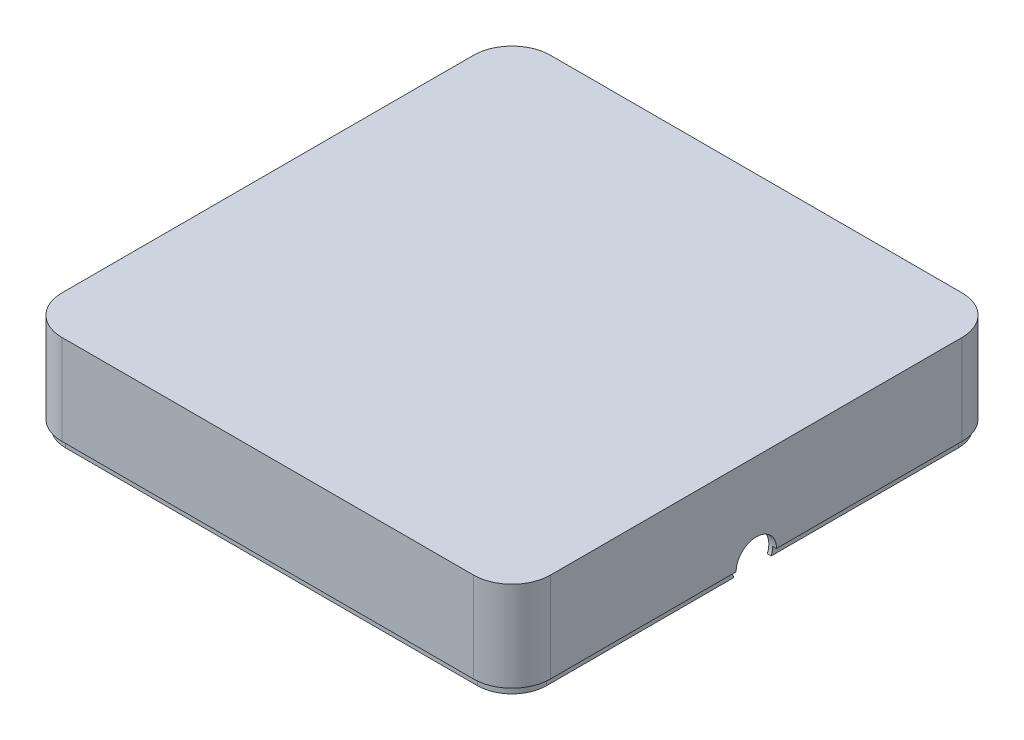
SolidWorks part; units mm, degrees
ref_plane "Front" through (0, 0, 0) normal (0, 0, 1) x (1, 0, 0)
ref_plane "Top" through (0, 0, 0) normal (0, 1, 0) x (1, 0, 0)
ref_plane "Right" through (0, 0, 0) normal (1, 0, 0) x (0, 0, -1)
sketch "Sketch1" plane through (0, 0, 0) normal (0, 0, 1) x (1, 0, 0)
  line L1 (0, 0) -> (127, 0)
  line L2 (0, 0) -> (0, -25.4)
  line L3 (0, -25.4) -> (127, -25.4)
  line L4 (127, 0) -> (127, -25.4)
  dimension "D1" = 127
  dimension "D2" = 25.4
extrude "Boss-Extrude1" add sketch "Sketch1" along normal blind 127
fillet "Fillet1" radius 10 4 edges at (0, -12.7, 127) (0, -12.7, 0) (127, -12.7, 0) (127, -12.7, 127)
shell "Shell1" thickness 2 removed face at (63.5, -25.4, 63.5)
sketch "Sketch3" plane through (0, -25.4, 0) normal (0, -1, 0) x (1, 0, 0)
  line L4 (117, 127) -> (10, 127)
  line L5 (0, 117) -> (0, 10)
  line L6 (10, 0) -> (117, 0)
  line L7 (127, 10) -> (127, 117)
  line L8 (117, 127) -> (10, 127)
  line L9 (0, 117) -> (0, 10)
  line L10 (10, 0) -> (117, 0)
  line L11 (127, 10) -> (127, 117)
  line L16 (117, 126) -> (10, 126)
  line L17 (1, 117) -> (1, 10)
  line L18 (10, 1) -> (117, 1)
  line L19 (126, 10) -> (126, 117)
  line L20 (117, 126) -> (10, 126)
  line L21 (1, 117) -> (1, 10)
  line L22 (10, 1) -> (117, 1)
  line L23 (126, 10) -> (126, 117)
  arc A4 (10, 127) -> (0, 117) centre (10, 117) ccw
  arc A5 (0, 10) -> (10, 0) centre (10, 10) ccw
  arc A6 (117, 0) -> (127, 10) centre (117, 10) ccw
  arc A7 (127, 117) -> (117, 127) centre (117, 117) ccw
  arc A8 (10, 127) -> (0, 117) centre (10, 117) ccw
  arc A9 (0, 10) -> (10, 0) centre (10, 10) ccw
  arc A10 (117, 0) -> (127, 10) centre (117, 10) ccw
  arc A11 (127, 117) -> (117, 127) centre (117, 117) ccw
  arc A16 (10, 126) -> (1, 117) centre (10, 117) ccw
  arc A17 (1, 10) -> (10, 1) centre (10, 10) ccw
  arc A18 (117, 1) -> (126, 10) centre (117, 10) ccw
  arc A19 (126, 117) -> (117, 126) centre (117, 117) ccw
  arc A20 (10, 126) -> (1, 117) centre (10, 117) ccw
  arc A21 (1, 10) -> (10, 1) centre (10, 10) ccw
  arc A22 (117, 1) -> (126, 10) centre (117, 10) ccw
  arc A23 (126, 117) -> (117, 126) centre (117, 117) ccw
  dimension "D1" = 0
  dimension "D2" = 1
extrude "Cut-Extrude1" cut sketch "Sketch3" against normal blind 2
sketch "Sketch5" plane through (127, 0, 0) normal (1, 0, 0) x (0, 0, -1)
  line L0 (-10, -23.4) -> (-117, -23.4) construction
  circle A0 centre (-63.5, -23.4) radius 5.25
extrude "Cut-Extrude3" cut sketch "Sketch5" against normal blind 4
sketch "Sketch6" plane through (0, 0, 0) normal (0, 0, -1) x (-1, 0, 0)
  line L1 (-23.2148, -42.6075) -> (-38.2148, -42.6075)
  line L2 (-23.2148, -42.6075) -> (-23.2148, -7.6075)
  line L3 (-23.2148, -7.6075) -> (-38.2148, -7.6075)
  line L4 (-38.2148, -42.6075) -> (-38.2148, -7.6075)
extrude "Cut-Extrude4" cut sketch "Sketch6" against normal up to next
